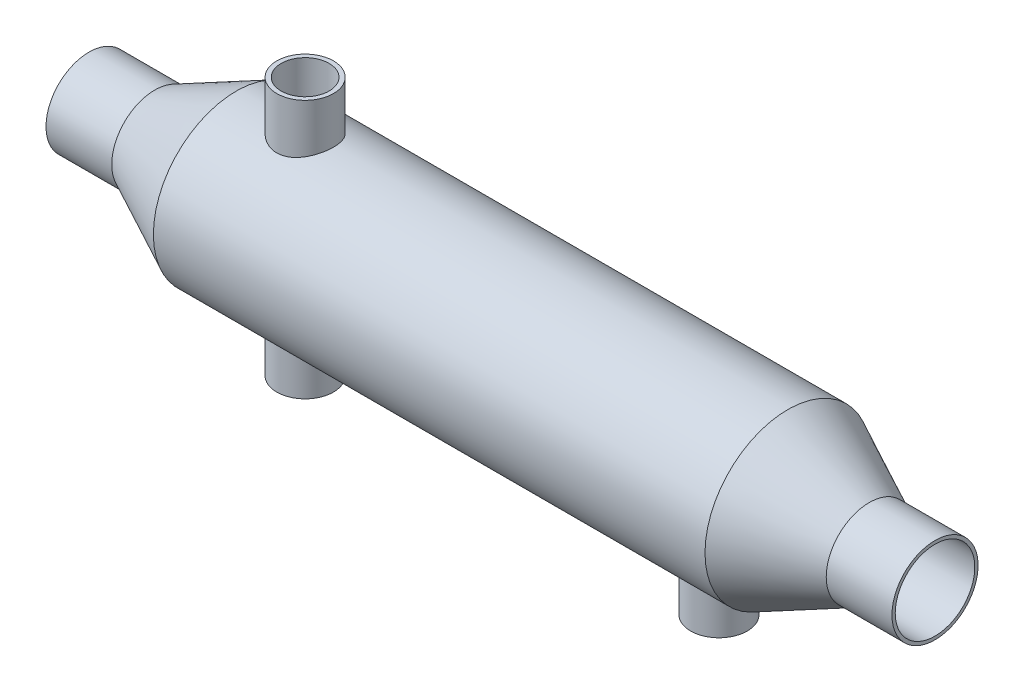
SolidWorks part; units mm, degrees
ref_plane "Alzado" through (0, 0, 0) normal (0, 0, 1) x (1, 0, 0)
ref_plane "Planta" through (0, 0, 0) normal (0, 1, 0) x (1, 0, 0)
ref_plane "Vista lateral" through (0, 0, 0) normal (1, 0, 0) x (0, 0, -1)
sketch "Croquis2" plane through (0, 0, 0) normal (0, 1, 0) x (1, 0, 0)
  line L0 (-388, 0) -> (388, 0)
  line L1 (388, 0) -> (388, -39.5)
  line L2 (388, -39.5) -> (327.69, -39.5)
  line L3 (-253, -76) -> (253, -76)
  line L4 (253, -76) -> (327.69, -39.5)
  line L5 (0, 0) -> (0, -76) construction
  line L6 (-388, 0) -> (-388, -39.5)
  line L7 (-388, -39.5) -> (-327.69, -39.5)
  line L8 (-253, -76) -> (-327.69, -39.5)
  point P0 (0, -76)
  point P4 (0, 0)
  point P11 (0, -76)
  dimension "D1" = 776
  dimension "D2" = 39.5
  dimension "D3" = 60.31
  dimension "D4" = 76
  dimension "D5" = 506
revolve "Revolución1" add sketch "Croquis2" angle 360 about L0
sketch "Croquis3" plane through (0, 0, 0) normal (0, 0, 1) x (1, 0, 0)
  line L0 (-253, -76) -> (253, -76) construction
  line L2 (189.8, -76) -> (215.8, -76)
  line L3 (189.8, -76) -> (189.8, -118.59)
  line L4 (189.8, -118.59) -> (215.8, -118.59)
  line L5 (215.8, -76) -> (215.8, -118.59)
  point P0 (189.8, -76)
  dimension "D1" = 198.2
  dimension "D2" = 26
  dimension "D3" = 42.59
revolve "Revolución2" add sketch "Croquis3" angle 360 about L3
sketch "Croquis4" plane through (0, 0, 0) normal (0, 1, 0) x (1, 0, 0)
  line L0 (-388, 0) -> (388, 0)
  line L1 (388, -39.5) -> (388, 39.5) construction
  line L2 (388, 0) -> (388, -36.5)
  line L3 (-252.305, -73) -> (252.305, -73)
  line L4 (388, -36.5) -> (327, -36.5)
  line L5 (252.305, -73) -> (327, -36.5)
  line L6 (0, 0) -> (0, 168.5165) construction
  line L7 (-388, 0) -> (-388, -36.5)
  line L8 (-388, -36.5) -> (-327, -36.5)
  line L9 (-252.305, -73) -> (-327, -36.5)
  point P0 (0, -73)
  point P6 (0, 0)
  point P11 (0, -73)
  dimension "D1" = 36.5
  dimension "D2" = 73
  dimension "D3" = 504.61
  dimension "D4" = 61
revolve "Cortar-Revolución1" cut sketch "Croquis4" angle 360 about L0
sketch "Croquis7" plane through (0, -76, 0) normal (0, 1, 0) x (1, 0, 0)
  circle A0 centre (189.8, 0) radius 26
  circle A1 centre (189.8, 0) radius 22
sketch "Croquis8" plane through (0, -118.59, 0) normal (0, -1, 0) x (1, 0, 0)
  circle A0 centre (189.8, 0) radius 22
extrude "Cortar-Extruir2" cut sketch "Croquis8" against normal blind 69
extrude "Saliente-Extruir4" add sketch "Croquis7" along normal up to surface (4.5857 mm away) up to face at (185.7355, -72.8596, 21.6213)
sketch "Croquis9" plane through (0, 0, 0) normal (0, 0, 1) x (1, 0, 0)
  line L0 (253, 76) -> (-253, 76) construction
  line L1 (-388, 39.5) -> (-388, -39.5) construction
  line L3 (-189.8, 76) -> (-163.8, 76)
  line L4 (-189.8, 76) -> (-189.8, 118.59)
  line L5 (-189.8, 118.59) -> (-163.8, 118.59)
  line L6 (-163.8, 76) -> (-163.8, 118.59)
  point P0 (-189.8, 76)
  dimension "D1" = 198.2
  dimension "D2" = 26
  dimension "D3" = 42.59
sketch "Croquis10" plane through (0, 0, 0) normal (0, 0, 1) x (1, 0, 0)
  line L0 (-253, -76) -> (163.8, -76) construction
  line L2 (-189.8, -76) -> (-163.8, -76)
  line L3 (-189.8, -76) -> (-189.8, -118.59)
  line L4 (-189.8, -118.59) -> (-163.8, -118.59)
  line L5 (-163.8, -76) -> (-163.8, -118.59)
  point P0 (-189.8, -76)
  dimension "D1" = 26
  dimension "D2" = 42.59
revolve "Revolución3" add sketch "Croquis9" angle 360 about L4
revolve "Revolución4" add sketch "Croquis10" angle 360 about L3
sketch "Croquis11" plane through (0, 118.59, 0) normal (0, 1, 0) x (1, 0, 0)
  circle A0 centre (-189.8, 0) radius 22
extrude "Cortar-Extruir3" cut sketch "Croquis11" against normal blind 220
sketch "Croquis12" plane through (0, -76, 0) normal (0, 1, 0) x (1, 0, 0)
  circle A0 centre (-189.8, 0) radius 26
  circle A1 centre (-189.8, 0) radius 22
extrude "Saliente-Extruir5" add sketch "Croquis12" along normal up to surface (4.5857 mm away) up to face at (-185.7355, -72.8596, -21.6213)
sketch "Croquis13" plane through (0, 76, 0) normal (0, -1, 0) x (1, 0, 0)
  circle A0 centre (-189.8, 0) radius 26
  circle A1 centre (-189.8, 0) radius 22
extrude "Saliente-Extruir6" add sketch "Croquis13" along normal up to surface (4.5857 mm away) up to face at (-193.8645, 72.8596, -21.6213)
